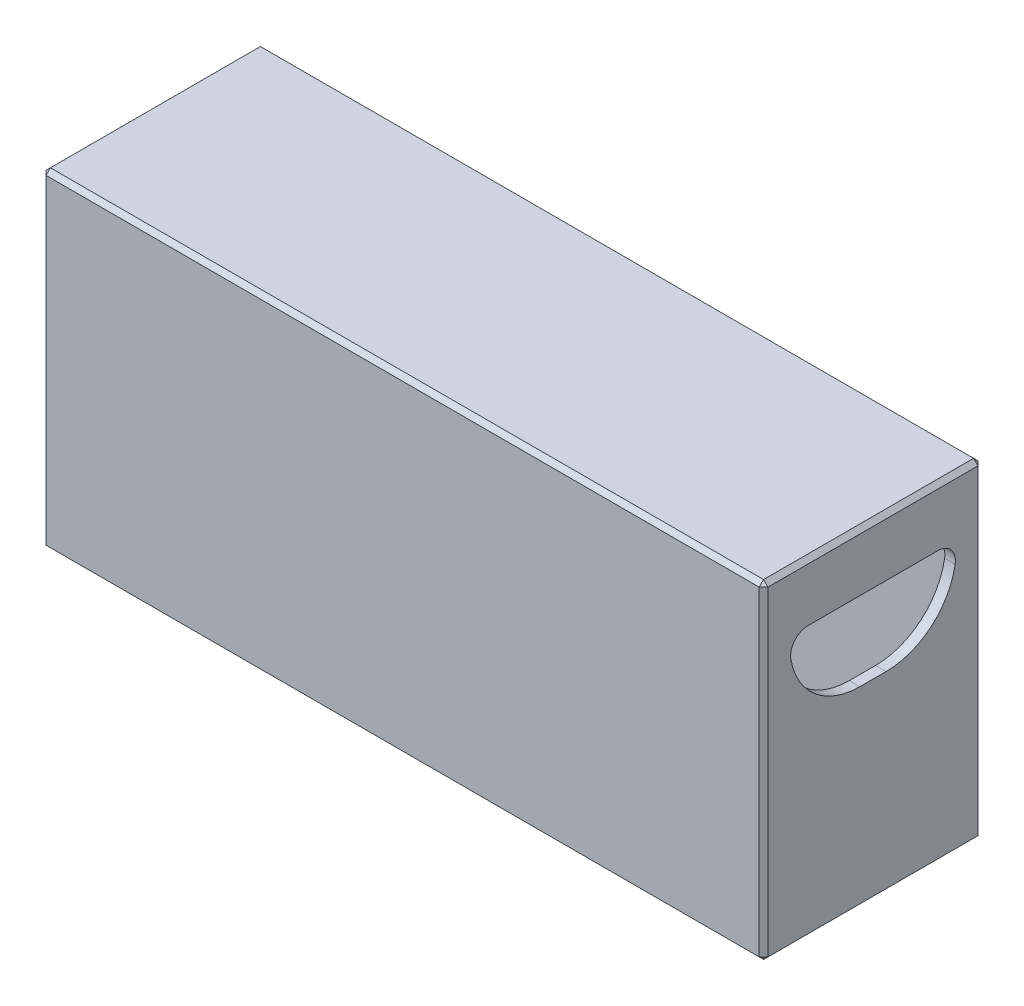
SolidWorks part; units mm, degrees
ref_plane "Front Plane" through (0, 0, 0) normal (0, 0, 1) x (1, 0, 0)
ref_plane "Top Plane" through (0, 0, 0) normal (0, 1, 0) x (1, 0, 0)
ref_plane "Right Plane" through (0, 0, 0) normal (1, 0, 0) x (0, 0, -1)
sketch "Sketch1" plane through (0, 0, 0) normal (0, 1, 0) x (1, 0, 0)
  line L0 (-41.25, 12.5) -> (41.25, 12.5)
  line L1 (-40.05, -11.3) -> (40.05, -11.3)
  line L2 (-40.05, -11.3) -> (-40.05, 11.3)
  line L3 (-40.05, 11.3) -> (40.05, 11.3)
  line L4 (40.05, -11.3) -> (40.05, 11.3)
  line L5 (-40.05, -11.3) -> (40.05, 11.3) construction
  line L6 (-40.05, 11.3) -> (40.05, -11.3) construction
  line L7 (41.25, -12.5) -> (41.25, 12.5)
  line L8 (-41.25, -12.5) -> (41.25, -12.5)
  line L9 (-41.25, -12.5) -> (-41.25, 12.5)
  point P0 (0, 0)
  dimension "D1" = 80.1
  dimension "D2" = 22.6
  dimension "D3" = 1.2
extrude "Boss-Extrude1" add sketch "Sketch1" along normal blind 23.2
extrude "Boss-Extrude2" add sketch "Sketch1<2>" against normal blind 2 contours L1 L4 L3 L2 | L9 L8 L7 L0 L4 L1 L2 L3 region at (0, 0, -11.638) region at (0, 0, 0)
sketch "Sketch1<2>" plane through (0, 0, 0) normal (0, 1, 0) x (1, 0, 0) same geometry as "Sketch1"
sketch "Sketch2" plane through (0, 0, 0) normal (0, 1, 0) x (1, 0, 0)
  line L0 (-37.55, 11.3) -> (-37.55, 5.75)
  line L1 (40.05, 11.3) -> (-40.05, 11.3) construction
  line L2 (-37.55, 5.75) -> (-40.05, 5.75)
  line L3 (-40.05, 11.3) -> (-40.05, -11.3) construction
  line L4 (0, -55) -> (0, 55) construction
  line L5 (-40.05, -5.75) -> (-37.55, -5.75)
  line L6 (-37.55, -5.75) -> (-37.55, -11.3)
  line L7 (-40.05, -11.3) -> (40.05, -11.3) construction
  line L12 (-37.55, 11.3) -> (-40.05, 11.3)
  line L13 (-40.05, 11.3) -> (-40.05, 5.75)
  line L14 (-40.05, -5.75) -> (-40.05, -11.3)
  line L15 (-40.05, -11.3) -> (-37.55, -11.3)
  line L16 (40.05, -11.3) -> (37.55, -11.3)
  line L17 (40.05, -5.75) -> (40.05, -11.3)
  line L18 (40.05, 11.3) -> (40.05, 5.75)
  line L19 (37.55, 11.3) -> (40.05, 11.3)
  line L20 (37.55, -5.75) -> (37.55, -11.3)
  line L21 (40.05, -5.75) -> (37.55, -5.75)
  line L22 (37.55, 5.75) -> (40.05, 5.75)
  line L23 (37.55, 11.3) -> (37.55, 5.75)
  dimension "D1" = 11.5
  dimension "D2" = 2.5
extrude "Boss-Extrude3" add sketch "Sketch2" along normal blind 5
sketch "Sketch3" plane through (0, 23.2, 0) normal (0, 1, 0) x (1, 0, 0)
  line L1 (-35, 11.3) -> (35, 11.3)
  line L3 (37.55, 11.3) -> (-37.55, 11.3) construction
  point P0 (0, 0)
  point P4 (0, 11.3)
  dimension "D1" = 70
sketch "Sketch4" plane through (0, 0, 0) normal (1, 0, 0) x (0, 0, -1)
  line L6 (10.1, 23.2) -> (11.3, 24.4)
  line L7 (11.3, 24.4) -> (12.5, 24.4)
  line L8 (12.5, 24.4) -> (12.5, 23.2)
  line L9 (12.5, 23.2) -> (10.1, 23.2)
  line L10 (11.3, 23.2) -> (11.3, 24.4) construction
  dimension "D1" = 1.2
  dimension "D2" = 45
sweep "Sweep2" add profiles "Sketch4" path "Sketch3"
mirror "Mirror1" about plane through (0, 0, 0) normal (0, 0, 1) of "Sweep2"
sketch "Sketch8" plane through (0, 23.2, 0) normal (0, 1, 0) x (1, 0, 0)
  line L0 (-40.05, 11.3) -> (-40.05, -11.3)
  line L1 (-41.25, 12.5) -> (41.25, 12.5)
  line L2 (-41.25, 12.5) -> (-41.25, -12.5)
  line L3 (-41.25, -12.5) -> (41.25, -12.5)
  line L4 (41.25, 12.5) -> (41.25, -12.5)
  line L5 (-40.05, -11.3) -> (40.05, -11.3)
  line L6 (40.05, 11.3) -> (40.05, -11.3)
  line L7 (-40.05, 11.3) -> (40.05, 11.3)
  dimension "D1" = 1.2
extrude "Boss-Extrude4" add sketch "Sketch8" along normal blind 11.2
sketch "Sketch10" plane through (0, 34.4, 0) normal (0, 1, 0) x (1, 0, 0)
  line L4 (-41.25, 12.5) -> (-41.25, -12.5)
  line L5 (-41.25, -12.5) -> (41.25, -12.5)
  line L6 (41.25, -12.5) -> (41.25, 12.5)
  line L7 (41.25, 12.5) -> (-41.25, 12.5)
  line L8 (-41.25, 12.5) -> (-41.25, -12.5)
  line L9 (-41.25, -12.5) -> (41.25, -12.5)
  line L10 (41.25, -12.5) -> (41.25, 12.5)
  line L11 (41.25, 12.5) -> (-41.25, 12.5)
  dimension "D1" = 0
extrude "Boss-Extrude6" add sketch "Sketch10" along normal blind 1.2
sketch "Sketch11" plane through (41.25, 0, 0) normal (1, 0, 0) x (0, 0, -1)
  line L0 (12.5, 35.6) -> (12.5, -2) construction
  line L3 (-9.5, 20) -> (9.5, 20)
  line L4 (-9.5, 20) -> (-9.5, 29)
  line L5 (-9.5, 29) -> (9.5, 29)
  line L6 (9.5, 20) -> (9.5, 29)
  line L7 (-9.5, 20) -> (9.5, 29) construction
  line L8 (-9.5, 29) -> (9.5, 20) construction
  line L10 (-12.5, 35.6) -> (-12.5, -2) construction
  line L11 (-12.5, -2) -> (12.5, -2) construction
  point P0 (0, 24.5)
  dimension "D1" = 3
  dimension "D2" = 22
  dimension "D3" = 3
  dimension "D4" = 9
extrude "Cut-Extrude1" cut sketch "Sketch11" against normal blind 1.2
fillet "Fillet1" radius 8 2 edges at (40.65, 20, -9.5) (40.65, 20, 9.5)
fillet "Fillet2" radius 2 2 edges at (40.65, 29, 9.5) (40.65, 29, -9.5)
chamfer "Chamfer1" distance 0.5 angle 45 12 edges at (0, -2, -12.5) (41.25, 16.8, -12.5) (0, 35.6, -12.5) (-41.25, 16.8, -12.5) (-41.25, -2, 0) (0, -2, 12.5) (41.25, -2, 0) (41.25, 35.6, 0) (41.25, 16.8, 12.5) (0, 35.6, 12.5) (-41.25, 16.8, 12.5) (-41.25, 35.6, 0)
chamfer "Chamfer2" distance 2 angle 45 4 edges at (0, 34.4, 11.3) (40.05, 34.4, 0) (0, 34.4, -11.3) (-40.05, 34.4, 0)
sketch "Sketch12" plane through (-41.25, 0, 0) normal (-1, 0, 0) x (0, 0, 1)
  line L0 (12, -2) -> (-12, -2) construction
  circle A0 centre (0, 24) radius 2
  point P2 (0, 0)
  dimension "D1" = 4
  dimension "D2" = 26
extrude "Cut-Extrude2" cut sketch "Sketch12" against normal blind 1.2
